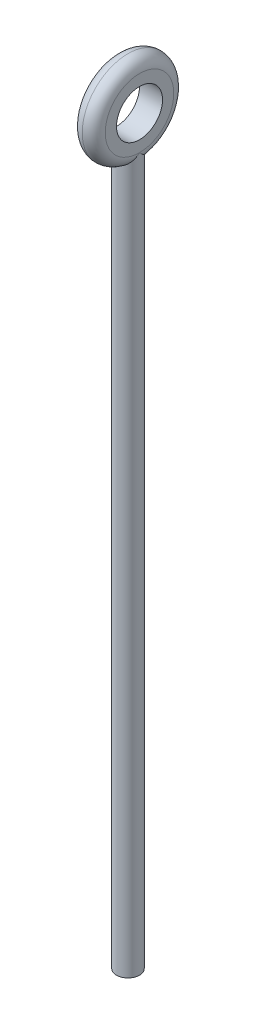
SolidWorks part; units mm, degrees
ref_plane "Front Plane" through (0, 0, 0) normal (0, 0, 1) x (1, 0, 0)
ref_plane "Top Plane" through (0, 0, 0) normal (0, 1, 0) x (1, 0, 0)
ref_plane "Right Plane" through (0, 0, 0) normal (1, 0, 0) x (0, 0, -1)
sketch "Sketch1" plane through (0, 0, 0) normal (1, 0, 0) x (0, 0, -1)
  circle A0 centre (0, 0) radius 6.35
  circle A1 centre (0, 0) radius 12.626
  dimension "D1" = 12.7
extrude "Boss-Extrude1" add sketch "Sketch1" along normal blind 6.35
sketch "Sketch3" plane through (6.35, 0, 0) normal (1, 0, 0) x (0, 0, -1)
  line L0 (-8.9948, -8.8606) -> (-8.9948, -15.4523)
  line L1 (-8.9948, -15.4523) -> (10.7986, -15.4523)
  line L2 (10.7986, -15.4523) -> (10.7986, -6.5427)
  line L3 (10.7986, -6.5427) -> (-8.9948, -6.5427)
  line L4 (-8.9948, -6.5427) -> (-8.9948, -8.8606)
  circle A0 centre (0, 0) radius 12.626 construction
extrude "Boss-Extrude2" add sketch "Sketch3" against normal blind 6.35
sketch "Sketch4" plane through (0, -15.4523, 0) normal (0, -1, 0) x (1, 0, 0)
  circle A0 centre (3.175, 0) radius 3.175
extrude "Boss-Extrude3" add sketch "Sketch4" along normal blind 50.8
sketch "Sketch5" plane through (6.35, 0, 0) normal (1, 0, 0) x (0, 0, -1)
  line L0 (-8.9948, -8.8606) -> (-8.9948, -15.4523)
  line L1 (-8.9948, -15.4523) -> (10.7986, -15.4523)
  line L2 (10.7986, -15.4523) -> (10.7986, -6.5427)
  arc A0 (-8.9948, -8.8606) -> (10.7986, -6.5427) centre (0, 0) ccw
extrude "Cut-Extrude1" cut sketch "Sketch5" against normal blind 6.35
sketch "Sketch7" plane through (0, -66.2523, 0) normal (0, -1, 0) x (1, 0, 0)
  circle A0 centre (3.175, 0) radius 3.175
extrude "Boss-Extrude4" add sketch "Sketch7" against normal blind 57.15
extrude "Cut-Extrude2" cut sketch "Sketch7<2>" against normal blind 25.4
sketch "Sketch7<2>" plane through (0, -66.2523, 0) normal (0, -1, 0) x (1, 0, 0) same geometry as "Sketch7"
fillet "Fillet1" radius 3.175 2 edges at (6.35, 0, -12.626) (0, 0, -12.626)
extrude "Boss-Extrude5" add sketch "Sketch7<3>" against normal blind 25.4 and the other way blind 139.7
sketch "Sketch7<3>" plane through (0, -66.2523, 0) normal (0, -1, 0) x (1, 0, 0) same geometry as "Sketch7"
